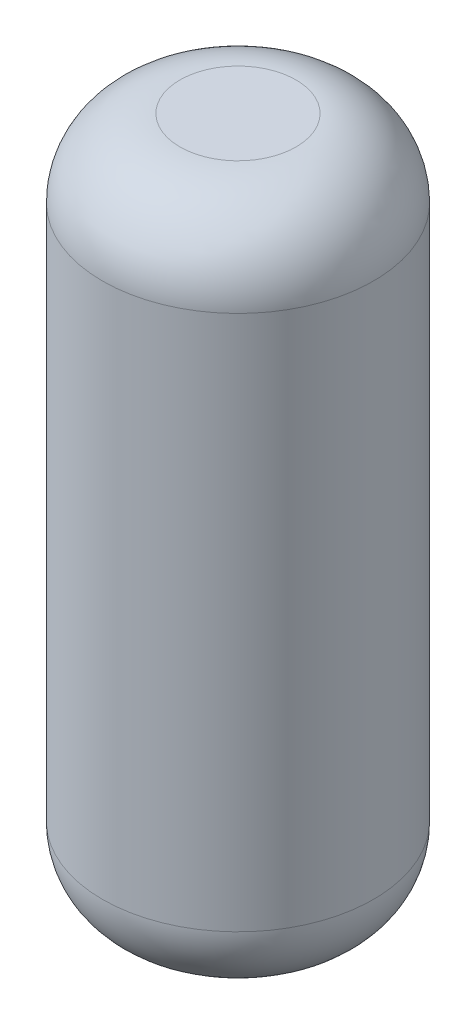
SolidWorks part; units mm, degrees
ref_plane "Front Plane" through (0, 0, 0) normal (0, 0, 1) x (1, 0, 0)
ref_plane "Top Plane" through (0, 0, 0) normal (0, 1, 0) x (1, 0, 0)
ref_plane "Right Plane" through (0, 0, 0) normal (1, 0, 0) x (0, 0, -1)
sketch "Sketch1" plane through (0, 0, 0) normal (0, 1, 0) x (1, 0, 0)
  circle A0 centre (0, 0) radius 2.1
  dimension "D1" = 4.2
extrude "Boss-Extrude1" add sketch "Sketch1" along normal blind 10.7
fillet "Fillet1" radius 1.2 2 edges at (0, 0, 2.1) (0, 10.7, 2.1)
